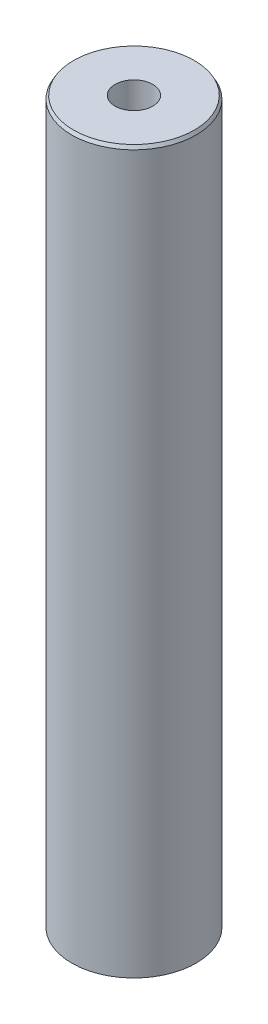
SolidWorks part; units mm, degrees
ref_plane "Front Plane" through (0, 0, 0) normal (0, 0, 1) x (1, 0, 0)
ref_plane "Top Plane" through (0, 0, 0) normal (0, 1, 0) x (1, 0, 0)
ref_plane "Right Plane" through (0, 0, 0) normal (1, 0, 0) x (0, 0, -1)
sketch "Sketch1" plane through (0, 0, 0) normal (0, 1, 0) x (1, 0, 0)
  circle A0 centre (0, 0) radius 42.5
  dimension "SHAFT_OD" = 85
extrude "Boss-Extrude1" add sketch "Sketch1" along normal blind 493.2274
sketch "Sketch2" plane through (0, 0, 0) normal (0, 1, 0) x (1, 0, 0)
  circle A0 centre (0, 0) radius 12.8854
  dimension "BORE_D" = 25.7708
extrude "Cut-Extrude1" cut sketch "Sketch2" along normal through all
chamfer "Chamfer1" distance 2.2384 angle 30 2 edges at (0, 493.2274, 42.5) (0, 0, 42.5) first distance on face at (0, 493.2274, 42.5) first distance on face at (0, 0, 12.8854)
